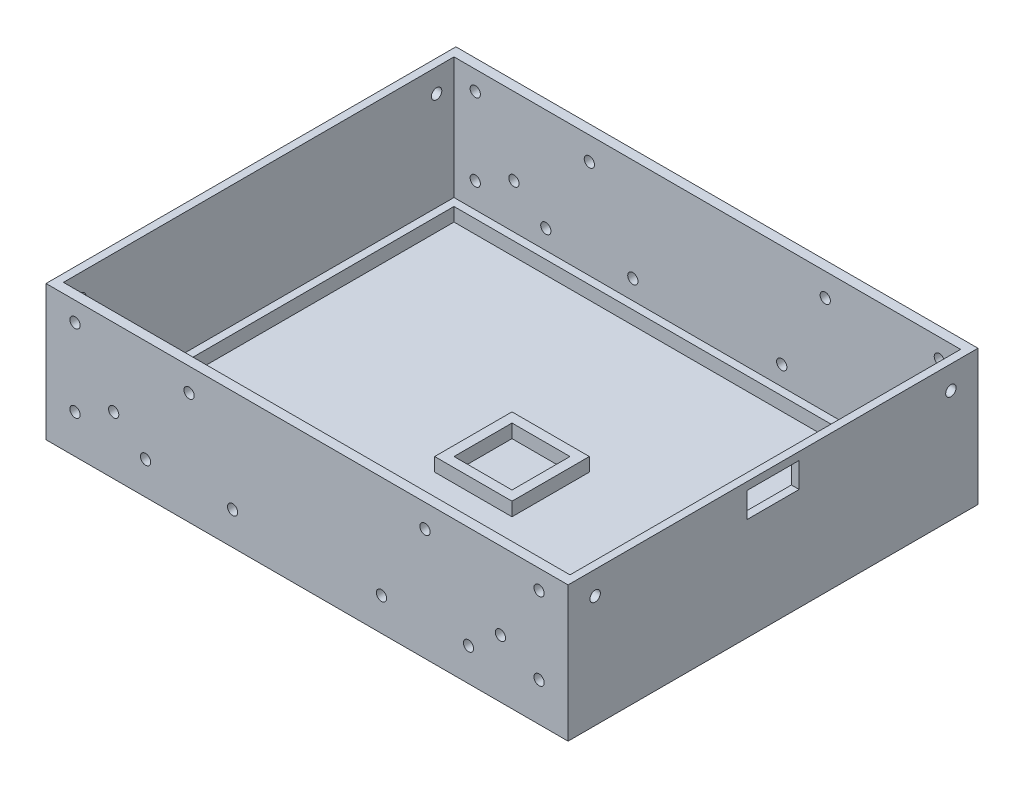
SolidWorks part; units mm, degrees
material "ABS"
ref_plane "Front Plane" through (0, 0, 0) normal (0, 0, 1) x (1, 0, 0)
ref_plane "Top Plane" through (0, 0, 0) normal (0, 1, 0) x (1, 0, 0)
ref_plane "Right Plane" through (0, 0, 0) normal (1, 0, 0) x (0, 0, -1)
sketch "Sketch1" plane through (0, 0, 0) normal (0, 1, 0) x (1, 0, 0)
  line L1 (-135, -106) -> (135, -106)
  line L2 (-135, -106) -> (-135, 106)
  line L3 (-135, 106) -> (135, 106)
  line L4 (135, -106) -> (135, 106)
  line L5 (-135, -106) -> (135, 106) construction
  line L6 (-135, 106) -> (135, -106) construction
  point P0 (0, 0)
  dimension "D1" = 270
  dimension "D2" = 212
extrude "Boss-Extrude1" add sketch "Sketch1" along normal blind 10
sketch "Sketch2" plane through (0, 10, 0) normal (0, 1, 0) x (1, 0, 0)
  line L5 (-131, -101) -> (131, -101)
  line L6 (-131, -101) -> (-131, 101)
  line L7 (-131, 101) -> (131, 101)
  line L16 (135, -106) -> (135, 106)
  line L17 (135, 106) -> (-135, 106)
  line L18 (-135, 106) -> (-135, -106)
  line L19 (-135, -106) -> (135, -106)
  line L20 (135, -106) -> (135, 106)
  line L21 (135, 106) -> (-135, 106)
  line L22 (-135, 106) -> (-135, -106)
  line L23 (-135, -106) -> (135, -106)
  line L24 (131, -101) -> (131, 101)
  line L25 (-131, -101) -> (131, 101) construction
  line L26 (-131, 101) -> (131, -101) construction
  point P2 (0, 0)
  dimension "D1" = 262
  dimension "D3" = 202
  dimension "D2" = 0
extrude "Boss-Extrude2" add sketch "Sketch2" along normal blind 70
sketch "Sketch3" plane through (0, 10, 0) normal (0, 1, 0) x (1, 0, 0)
  line L0 (-135, 115) -> (-135, -115)
  line L1 (-135, -115) -> (135, -115)
  line L2 (135, -115) -> (135, 115)
  line L3 (135, 115) -> (-135, 115)
  line L4 (-131, -101) -> (131, -101)
  line L13 (-15, -15) -> (15, -15)
  line L14 (-15, -15) -> (-15, 15)
  line L15 (-15, 15) -> (15, 15)
  line L16 (15, -15) -> (15, 15)
  line L17 (-15, -15) -> (15, 15) construction
  line L18 (-15, 15) -> (15, -15) construction
  line L19 (-20, -20) -> (20, -20)
  line L20 (-20, -20) -> (-20, 20)
  line L21 (-20, 20) -> (20, 20)
  line L22 (20, -20) -> (20, 20)
  line L23 (-20, -20) -> (20, 20) construction
  line L24 (-20, 20) -> (20, -20) construction
  line L28 (-131, -101) -> (131, -101)
  line L32 (131, -101) -> (131, 101)
  line L34 (131, -101) -> (131, 101)
  line L36 (131, 101) -> (-131, 101)
  line L37 (131, 101) -> (-131, 101)
  line L38 (-131, 101) -> (-131, -101)
  line L39 (-131, 101) -> (-131, -101)
  point P8 (0, 0)
  point P14 (0, 0)
  dimension "D3" = 30
  dimension "D4" = 5
  dimension "D1" = 0
extrude "Boss-Extrude3" add sketch "Sketch3" along normal blind 7 contours L19 L22 L21 L20 L16 L13 L14 L15 | L3 L2 L1 L0 region at (-19.4343, 10, 0)
chamfer "Chamfer1" distance 10 angle 45 4 edges at (0, 0, -106) (-135, 0, 0) (0, 0, 106) (135, 0, 0)
sketch "Sketch4" plane through (0, 0, 106) normal (0, 0, 1) x (1, 0, 0)
  line L0 (38.5, 27) -> (83.5, 27) construction
  line L1 (-135, 10) -> (135, 10) construction
  circle A0 centre (83.5, 27) radius 2.65
  circle A1 centre (38.5, 27) radius 2.65
  circle A2 centre (61, 68) radius 2.65
  point P6 (61, 27)
  dimension "D1" = 5.3
  dimension "D2" = 45
  dimension "D3" = 41
  dimension "D4" = 17
  dimension "D5" = 61
extrude "Cut-Extrude1" cut sketch "Sketch4" against normal up to surface (5 mm away) up to face at (0, 45, 101)
ref_axis "Axis1" through (0, 84, 0) along (0, -1, 0)
pattern_circular "CirPattern1" count 2 over 360 about axis through (0, 84, 0) along (0, -1, 0) of "Cut-Extrude1"
mirror "Mirror2" about plane through (0, 0, 0) normal (1, 0, 0) of "CirPattern1"
sketch "Sketch5" plane through (0, 0, 106) normal (0, 0, 1) x (1, 0, 0)
  line L0 (-135, 10) -> (135, 10) construction
  line L1 (-135, 80) -> (-135, 10) construction
  circle A0 centre (-120, 70) radius 2.65
  circle A1 centre (-120, 30) radius 2.65
  circle A2 centre (-100, 40) radius 2.65
  dimension "D1" = 5.3
  dimension "D2" = 40
  dimension "D3" = 20
  dimension "D4" = 15
  dimension "D5" = 30
  dimension "D6" = 20
extrude "Cut-Extrude2" cut sketch "Sketch5" against normal through all
mirror "Mirror1" about plane through (0, 0, 0) normal (1, 0, 0) of "Cut-Extrude2"
fillet "Fillet1" radius 7 4 edges at (0, 0, 96) (125, 0, 0) (0, 0, -96) (-125, 0, 0)
sketch "Sketch6" plane through (0, 10, 0) normal (0, 1, 0) x (1, 0, 0)
  line L0 (-127, 97) -> (-127, -97)
  line L1 (-127, -97) -> (127, -97)
  line L2 (127, -97) -> (127, 97)
  line L3 (127, 97) -> (-127, 97)
  line L4 (-131, -101) -> (131, -101)
  line L6 (-131, -101) -> (131, -101)
  line L16 (131, 101) -> (-131, 101)
  line L18 (131, 101) -> (-131, 101)
  line L20 (-131, 101) -> (-131, -101)
  line L21 (-131, 101) -> (-131, -101)
  line L22 (131, -101) -> (131, 101)
  line L23 (131, -101) -> (131, 101)
  dimension "D2" = 4
  dimension "D3" = 4
  dimension "D4" = 4
  dimension "D5" = 4
  dimension "D1" = 0
extrude "Boss-Extrude4" add sketch "Sketch6" along normal up to surface (7 mm away) up to face at (0, 17, 0)
sketch "Sketch7" plane through (135, 0, 0) normal (1, 0, 0) x (0, 0, -1)
  line L0 (0, 84) -> (0, -4) construction
  line L1 (-13.5, 76) -> (13.5, 76)
  line L2 (-13.5, 76) -> (-13.5, 63)
  line L3 (-13.5, 63) -> (13.5, 63)
  line L4 (13.5, 76) -> (13.5, 63)
  line L5 (-13.5, 76) -> (13.5, 63) construction
  line L6 (-13.5, 63) -> (13.5, 76) construction
  line L7 (-106, 80) -> (106, 80) construction
  point P0 (0, 69.5)
  dimension "D1" = 27
  dimension "D2" = 13
  dimension "D3" = 4
extrude "Cut-Extrude3" cut sketch "Sketch7" against normal up to surface (4 mm away) up to face at (131, 48.5, 0)
sketch "Sketch8" plane through (-135, 0, 0) normal (-1, 0, 0) x (0, 0, 1)
  line L0 (-106, 80) -> (-106, 10) construction
  line L1 (-106, 80) -> (106, 80) construction
  circle A0 centre (-92, 68) radius 2.7
  dimension "D2" = 5.4
  dimension "D1" = 14
  dimension "D3" = 12
extrude "Cut-Extrude4" cut sketch "Sketch8" against normal through all both
mirror "Mirror3" about plane through (0, 0, 0) normal (0, 0, 1) of "Cut-Extrude4"
